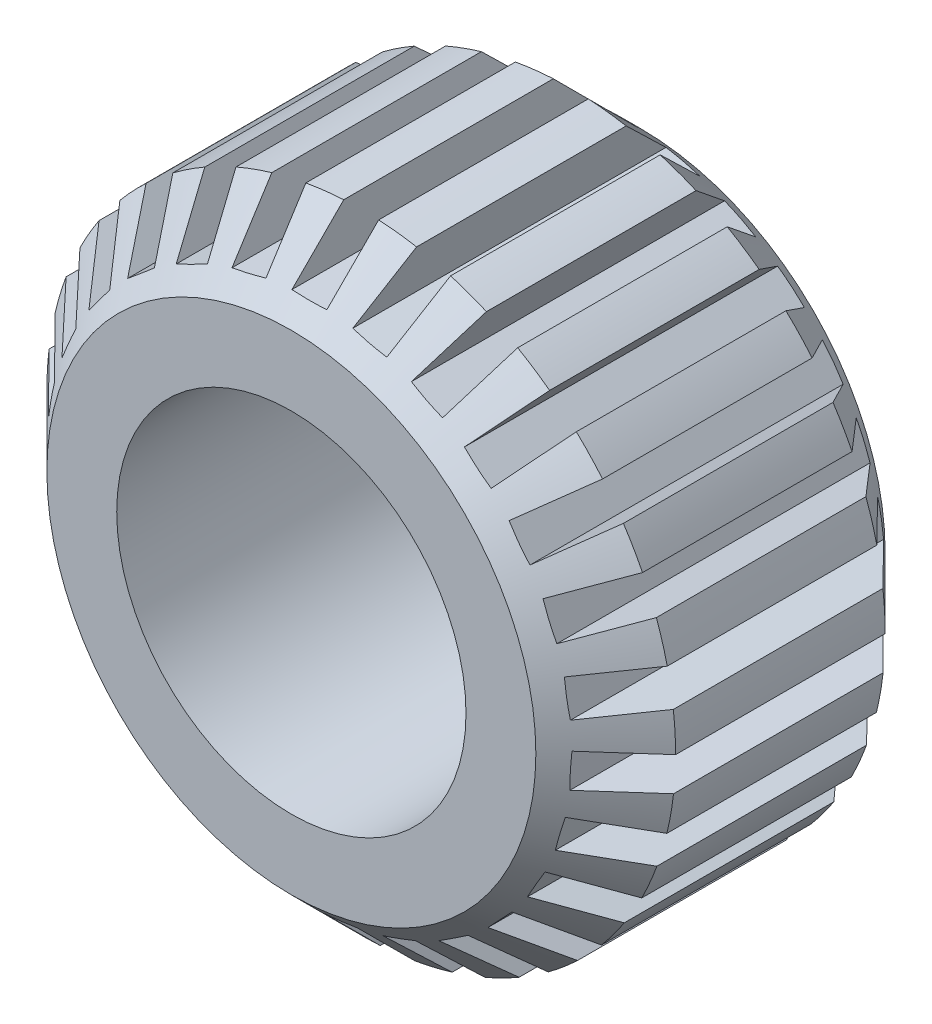
SolidWorks part; units mm, degrees
ref_plane "Front Plane" through (0, 0, 0) normal (0, 0, 1) x (1, 0, 0)
ref_plane "Top Plane" through (0, 0, 0) normal (0, 1, 0) x (1, 0, 0)
ref_plane "Right Plane" through (0, 0, 0) normal (1, 0, 0) x (0, 0, -1)
sketch "Sketch2" plane through (0, 0, 0) normal (0, 0, 1) x (1, 0, 0)
  circle A0 centre (0, 0) radius 5
  circle A1 centre (0, 0) radius 9
  circle A2 centre (0, 0) radius 1
  dimension "D1" = 10
  dimension "D2" = 4
  dimension "D3" = 4
extrude "Boss-Extrude1" add sketch "Sketch2" along normal blind 10 contours A1 A0 region at (-8.7454, 0, 0)
chamfer "Chamfer1" distance 2 angle 45 2 edges at (9, 0, 0) (9, 0, 10)
sketch "Sketch5" plane through (0, 0, 10) normal (0, 0, 1) x (1, 0, 0)
  line L1 (-0.5, 8.9861) -> (-0.5, 7.5)
  line L2 (0.5, 8.9861) -> (0.5, 7.5)
  line L3 (-0.5, 7.5) -> (0.5, 7.5)
  circle A0 centre (0, 0) radius 9
  point P3 (0, 9)
  point P4 (-0.5, 9)
  point P5 (-0.5, 0)
  point P6 (0.5, 9)
  point P7 (0.5, 0)
  dimension "D1" = 18
extrude "Cut-Extrude1" cut sketch "Sketch5" against normal through all and the other way through all contours L2 A0 L1 L3 region at (0, 8.2477, 10)
ref_axis "Axis1" through (0, 0, 10) along (0, 0, -1)
pattern_circular "CirPattern1" count 27 over 360 about axis through (0, 0, 10) along (0, 0, -1) of "Cut-Extrude1"
